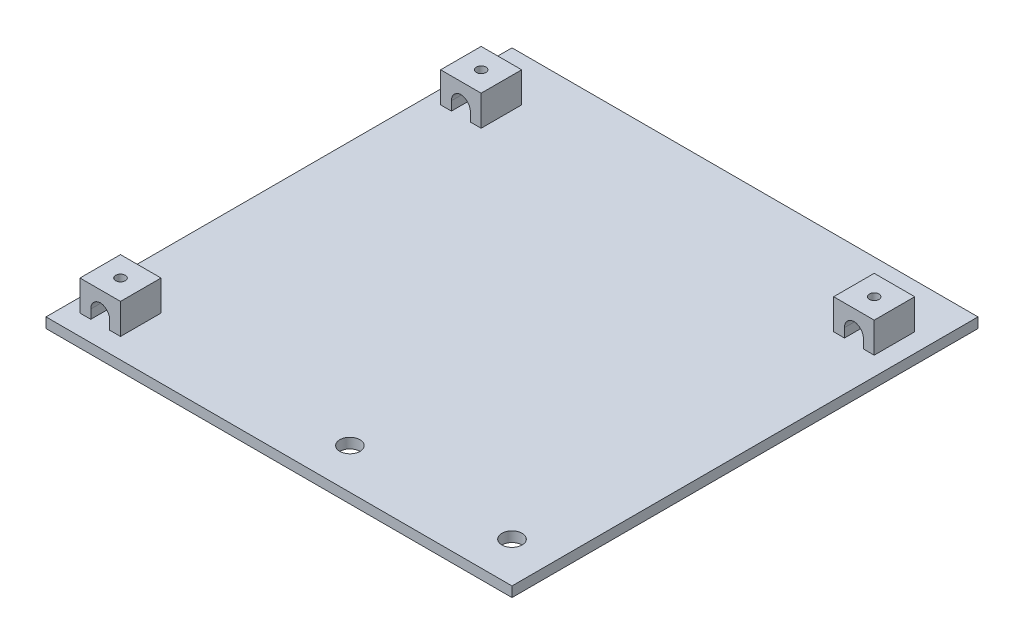
SolidWorks part; units mm, degrees
ref_plane "Front Plane" through (0, 0, 0) normal (0, 0, 1) x (1, 0, 0)
ref_plane "Top Plane" through (0, 0, 0) normal (0, 1, 0) x (1, 0, 0)
ref_plane "Right Plane" through (0, 0, 0) normal (1, 0, 0) x (0, 0, -1)
sketch "Sketch1" plane through (0, 0, 0) normal (0, 1, 0) x (1, 0, 0)
  line L1 (0, 0) -> (146.05, 0)
  line L2 (0, 0) -> (0, 146.05)
  line L3 (0, 146.05) -> (146.05, 146.05)
  line L4 (146.05, 0) -> (146.05, 146.05)
  circle A0 centre (133.35, 12.7) radius 3.175
  circle A1 centre (82.55, 12.7) radius 3.175
  dimension "D2" = 6.35
  dimension "D3" = 6.35
  dimension "D1" = 50.8
  dimension "D4" = 12.7
  dimension "D5" = 12.7
  dimension "D6" = 146.05
  dimension "D7" = 146.05
  dimension "D8" = 0
extrude "Boss-Extrude1" add sketch "Sketch1" along normal blind 3.175
sketch "Sketch2" plane through (0, 3.175, 0) normal (0, 1, 0) x (1, 0, 0)
  circle A0 centre (10.6489, 125.73) radius 1.5
  circle A1 centre (133.8389, 125.73) radius 1.5
  circle A2 centre (10.6489, 12.7) radius 1.5
  point P10 (82.55, 12.7)
  dimension "D1" = 3
  dimension "D2" = 3
  dimension "D3" = 3
  dimension "D6" = 0
  dimension "D7" = 0
  dimension "D4" = 123.19
  dimension "D5" = 113.03
  dimension "D8" = 0
sketch "Sketch4" plane through (0, 3.175, 0) normal (0, 1, 0) x (1, 0, 0)
  line L15 (4.2989, 19.05) -> (16.9989, 19.05)
  line L16 (4.2989, 19.05) -> (4.2989, 6.35)
  line L17 (4.2989, 6.35) -> (16.9989, 6.35)
  line L18 (16.9989, 19.05) -> (16.9989, 6.35)
  line L19 (4.2989, 132.08) -> (16.9989, 132.08)
  line L20 (4.2989, 132.08) -> (4.2989, 119.38)
  line L21 (4.2989, 119.38) -> (16.9989, 119.38)
  line L22 (16.9989, 132.08) -> (16.9989, 119.38)
  line L23 (127.4889, 132.08) -> (140.1889, 132.08)
  line L24 (127.4889, 132.08) -> (127.4889, 119.38)
  line L25 (127.4889, 119.38) -> (140.1889, 119.38)
  line L26 (140.1889, 132.08) -> (140.1889, 119.38)
  dimension "D1" = 6.35
  dimension "D2" = 6.35
  dimension "D3" = 6.35
  dimension "D4" = 6.35
  dimension "D5" = 6.35
  dimension "D6" = 6.35
  dimension "D7" = 6.35
  dimension "D8" = 6.35
  dimension "D9" = 6.35
  dimension "D10" = 6.35
  dimension "D11" = 6.35
  dimension "D12" = 6.35
extrude "Boss-Extrude4" add sketch "Sketch4" along normal blind 9.525
sketch "Sketch6" plane through (0, 0, -6.35) normal (0, 0, 1) x (1, 0, 0)
  line L1 (4.2989, 3.175) -> (7.6814, 3.175)
  line L2 (0, 3.175) -> (146.05, 3.175) construction
  line L3 (16.9989, 3.175) -> (13.6164, 3.175)
  line L4 (4.2989, 3.175) -> (16.9989, 3.175) construction
  line L5 (7.6814, 3.175) -> (7.6814, 9.175)
  line L6 (7.6814, 9.175) -> (13.6164, 9.175)
  line L7 (13.6164, 9.175) -> (13.6164, 3.175)
  line L8 (7.6814, 3.175) -> (13.6164, 3.175)
  line M4 (4.2989, 3.175) -> (16.9989, 3.175)
  dimension "D1" = 5.935
  dimension "D3" = 6
extrude "Cut-Extrude2" cut sketch "Sketch6" against normal blind 150 contours L7 L6 L5 M4 region at (10.6489, 6.175, -6.35)
sketch "Sketch7" plane through (0, 0, -119.38) normal (0, 0, 1) x (1, 0, 0)
  line L0 (127.4889, 3.175) -> (130.8714, 3.175)
  line L1 (127.4889, 3.175) -> (140.1889, 3.175) construction
  line L2 (130.8714, 3.175) -> (130.8714, 9.175)
  line L3 (140.1889, 3.175) -> (136.8064, 3.175)
  line L4 (0, 3.175) -> (146.05, 3.175) construction
  line L5 (135.3389, 3.175) -> (132.3389, 3.175) construction
  line L6 (136.8064, 3.175) -> (136.8064, 9.175)
  line L7 (136.8064, 9.175) -> (130.8714, 9.175)
  line L8 (130.8714, 3.175) -> (136.8064, 3.175)
  line M4 (127.4889, 3.175) -> (140.1889, 3.175)
  dimension "D1" = 5.935
  dimension "D2" = 6
extrude "Cut-Extrude3" cut sketch "Sketch7" against normal blind 15 contours L6 L7 L2 M4 region at (133.8389, 6.175, -119.38)
extrude "Cut-Extrude4" cut sketch "Sketch2" along normal blind 15
fillet "Fillet2" radius 3.175 6 edges at (136.8064, 9.175, -125.73) (130.8714, 9.175, -125.73) (13.6164, 9.175, -125.73) (7.6814, 9.175, -125.73) (13.6164, 9.175, -12.7) (7.6814, 9.175, -12.7)
equation "\"mountHoleDistance\" = 2in"
equation "\"D1@Sketch1\"=\"mountHoleDistance\""
equation "\"mountHoleDiameter\"= 0.25in"
equation "\"D2@Sketch1\"=\"mountHoleDiameter\""
equation "\"D3@Sketch1\"=\"mountHoleDiameter\""
